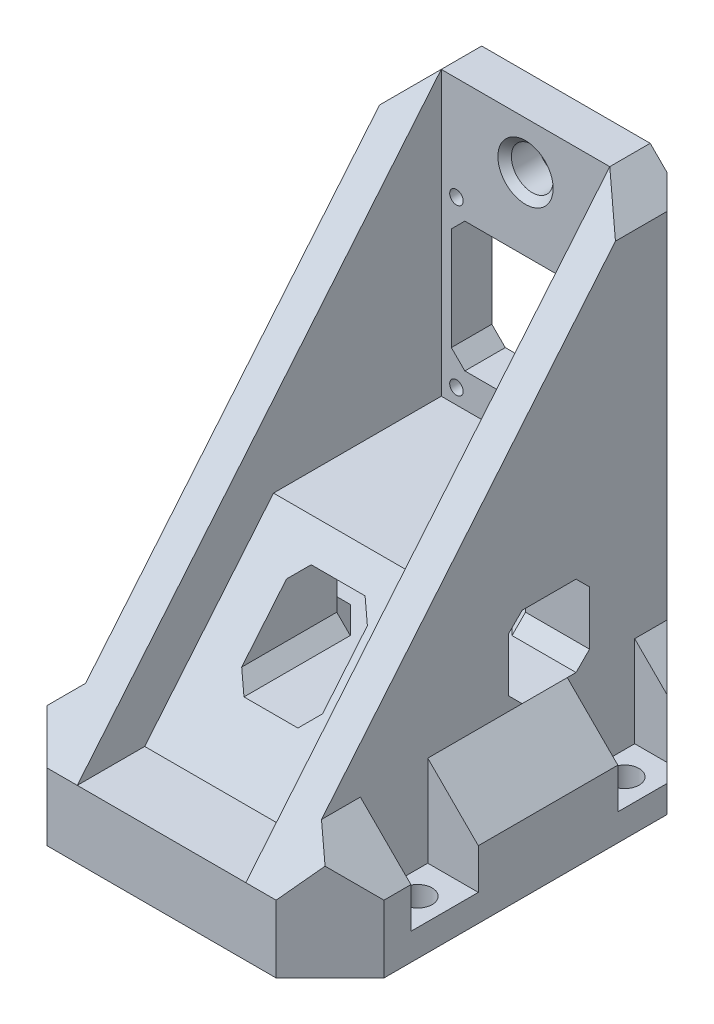
SolidWorks part; units mm, degrees
ref_plane "Front Plane" through (0, 0, 0) normal (0, 0, 1) x (1, 0, 0)
ref_plane "Top Plane" through (0, 0, 0) normal (0, 1, 0) x (1, 0, 0)
ref_plane "Right Plane" through (0, 0, 0) normal (1, 0, 0) x (0, 0, -1)
sketch "Sketch1" plane through (0, 0, 0) normal (0, 1, 0) x (1, 0, 0)
  line L1 (-25, 30) -> (25, 30)
  line L2 (-25, 30) -> (-25, -30)
  line L3 (-25, -30) -> (25, -30)
  line L4 (25, 30) -> (25, -30)
  line L5 (-25, 30) -> (25, -30) construction
  line L6 (-25, -30) -> (25, 30) construction
  point P0 (0, 0)
  dimension "D1" = 50
  dimension "D2" = 60
extrude "Boss-Extrude1" add sketch "Sketch1" along normal blind 10
sketch "Sketch2" plane through (0, 0, 0) normal (0, 1, 0) x (1, 0, 0)
  line L0 (-25, -30) -> (25, -30) construction
  line L1 (-21, -13) -> (21, -13) construction
  line L2 (-21, -13) -> (-21, 17.7) construction
  line L3 (-21, 17.7) -> (21, 17.7) construction
  line L4 (21, -13) -> (21, 17.7) construction
  line L5 (-21, -13) -> (21, 17.7) construction
  line L6 (-21, 17.7) -> (21, -13) construction
  circle A0 centre (-21, 17.7) radius 2.15
  circle A1 centre (-21, -13) radius 2.15
  circle A2 centre (21, 17.7) radius 2.15
  circle A3 centre (21, -13) radius 2.15
  point P0 (0, 2.35)
  dimension "D4" = 4.3
  dimension "D1" = 42
  dimension "D2" = 30.7
  dimension "D3" = 17
extrude "Cut-Extrude1" cut sketch "Sketch2" along normal blind 4
sketch "Sketch5" plane through (0, 10, 0) normal (0, 1, 0) x (1, 0, 0)
  line L0 (25, 30) -> (-25, 30) construction
  line L1 (-12.5, 24) -> (12.5, 24)
  line L2 (-12.5, 24) -> (-12.5, 30)
  line L3 (-12.5, 30) -> (12.5, 30)
  line L4 (12.5, 24) -> (12.5, 30)
  line L5 (-12.5, 24) -> (12.5, 30) construction
  line L6 (-12.5, 30) -> (12.5, 24) construction
  point P0 (0, 27)
  dimension "D1" = 6
  dimension "D2" = 25
extrude "Boss-Extrude3" add sketch "Sketch5" along normal blind 65
sketch "Sketch6" plane through (0, 0, -30) normal (0, 0, -1) x (-1, 0, 0)
  line L1 (-11, 38) -> (11, 38)
  line L2 (-11, 38) -> (-11, 57.25)
  line L3 (-11, 57.25) -> (11, 57.25)
  line L4 (11, 38) -> (11, 57.25)
  line L5 (-11, 38) -> (11, 57.25) construction
  line L6 (-11, 57.25) -> (11, 38) construction
  line L7 (-12.5, 75) -> (12.5, 75) construction
  point P0 (0, 47.625)
  dimension "D1" = 22
  dimension "D2" = 19.25
  dimension "D3" = 17.75
extrude "Cut-Extrude3" cut sketch "Sketch6" against normal up to next
sketch "Sketch7" plane through (0, 0, -24) normal (0, 0, 1) x (1, 0, 0)
  line L1 (-10.25, 35.25) -> (10.25, 35.25) construction
  line L2 (-10.25, 35.25) -> (-10.25, 59.7) construction
  line L3 (-10.25, 59.7) -> (10.25, 59.7) construction
  line L4 (10.25, 35.25) -> (10.25, 59.7) construction
  line L5 (-10.25, 35.25) -> (10.25, 59.7) construction
  line L6 (-10.25, 59.7) -> (10.25, 35.25) construction
  line L7 (-12.5, 75) -> (12.5, 75) construction
  circle A0 centre (10.25, 35.25) radius 1
  circle A1 centre (-10.25, 35.25) radius 1
  circle A2 centre (-10.25, 59.7) radius 1
  circle A3 centre (10.25, 59.7) radius 1
  point P0 (0, 47.475)
  dimension "D4" = 2
  dimension "D1" = 20.5
  dimension "D2" = 24.45
  dimension "D3" = 15.3
extrude "Cut-Extrude4" cut sketch "Sketch7" against normal blind 2.5
sketch "Sketch8" plane through (0, 0, -26.5) normal (0, 0, 1) x (1, 0, 0)
  circle A0 centre (-10.25, 59.7) radius 2
  circle A1 centre (10.25, 59.7) radius 2
  circle A2 centre (10.25, 35.25) radius 2
  circle A3 centre (-10.25, 35.25) radius 2
  dimension "D1" = 4
extrude "Cut-Extrude5" cut sketch "Sketch8" against normal up to next
sketch "Sketch9" plane through (12.5, 0, 0) normal (1, 0, 0) x (0, 0, -1)
  line L0 (30, 75) -> (24, 75)
  line L4 (-30, 10) -> (30, 10)
  line L5 (30, 10) -> (30, 75)
  line L6 (30, 75) -> (30, 10) construction
  line L8 (-30, 10) -> (24, 75)
extrude "Boss-Extrude4" add sketch "Sketch9" along normal blind 5
mirror "Mirror1" about plane through (0, 0, 0) normal (1, 0, 0) of "Boss-Extrude4"
chamfer "Chamfer1" distance 7.5 angle 45 2 edges at (17.5, 10, 0) (-17.5, 10, 0)
chamfer "Chamfer2" distance 10 angle 45 2 edges at (-25, 5, -30) (25, 5, -30)
chamfer "Chamfer4" distance 5.5 angle 45 1 edges at (0, 0, -30)
chamfer "Chamfer5" distance 5 angle 45 6 edges at (-15, 75, -24) (17.5, 75, -25.75) (-17.5, 75, -25.75) (16.25, 75, -28.75) (-16.25, 75, -28.75) (15, 75, -24)
chamfer "Chamfer7" distance 2 angle 45 4 edges at (-11, 57.25, -27) (-11, 38, -27) (11, 38, -27) (11, 57.25, -27)
sketch "Sketch10" plane through (0, 0, -30) normal (0, 0, -1) x (-1, 0, 0)
  circle A0 centre (0, 68) radius 3.1
  circle A1 centre (-10.25, 59.7) radius 2 construction
  dimension "D1" = 6.2
  dimension "D2" = 8.3
extrude "Cut-Extrude6" cut sketch "Sketch10" against normal up to next
chamfer "Chamfer8" distance 1 angle 45 2 edges at (-3.1, 68, -24) (-3.1, 68, -30)
sketch "Sketch11" plane through (-12.5, 0, 0) normal (1, 0, 0) x (0, 0, -1)
  line L0 (-20, 10) -> (24, 10)
  line L1 (24, 10) -> (24, 33)
  line L2 (24, 75) -> (24, 10) construction
  line L3 (24, 33) -> (-0.8923, 33)
  line L4 (30, 38) -> (24, 38) construction
  line L5 (-0.8923, 33) -> (-20, 10)
  line L7 (19.8462, 70) -> (-23.7692, 17.5) construction
  line L9 (-30, 10) -> (20, 10) construction
  dimension "D1" = 5
  dimension "D2" = 10
extrude "Boss-Extrude5" add sketch "Sketch11" along normal up to next
chamfer "Chamfer9" distance 8 angle 45 2 edges at (-25, 5, 30) (25, 5, 30)
sketch "Sketch12" plane through (0, 0, -30) normal (0, 0, -1) x (-1, 0, 0)
  line L1 (-6, 17.5) -> (6, 17.5)
  line L2 (-6, 17.5) -> (-6, 29.5)
  line L3 (-6, 29.5) -> (6, 29.5)
  line L4 (6, 17.5) -> (6, 29.5)
  line L5 (-6, 17.5) -> (6, 29.5) construction
  line L6 (-6, 29.5) -> (6, 17.5) construction
  point P0 (0, 23.5)
  dimension "D1" = 12
extrude "Cut-Extrude7" cut sketch "Sketch12" against normal up to next contours L2 L3 L4 L1
sketch "Sketch14" plane through (-6, 0, 0) normal (1, 0, 0) x (0, 0, -1)
  line L0 (-13.7692, 17.5) -> (30, 17.5) construction
  line L5 (30, 17.5) -> (30, 29.5) construction
  line L6 (-3.8, 29.5) -> (30, 29.5) construction
  line L7 (4, 17.5) -> (16, 17.5)
  line L8 (4, 17.5) -> (4, 29.5)
  line L9 (4, 29.5) -> (16, 29.5)
  line L10 (16, 17.5) -> (16, 29.5)
  line L11 (4, 17.5) -> (16, 29.5) construction
  line L12 (4, 29.5) -> (16, 17.5) construction
  point P0 (10, 23.5)
  dimension "D1" = 20
extrude "Cut-Extrude9" cut sketch "Sketch14" against normal up to next
mirror "Mirror2" about plane through (0, 0, 0) normal (1, 0, 0) of "Cut-Extrude9"
chamfer "Chamfer11" distance 2 angle 45 20 edges at (11.75, 29.5, -16) (6, 29.5, -23) (6, 23.5, -16) (11.75, 17.5, -16) (6, 17.5, -23) (-11.75, 17.5, -16) (-6, 17.5, -23) (-6, 23.5, -16) (-11.75, 29.5, -16) (-6, 29.5, -23) (11.75, 17.5, -4) (6, 17.5, 4.8846) (6, 23.5, -4) (11.75, 29.5, -4) (6, 29.5, -0.1) (-11.75, 17.5, -4) (-6, 17.5, 4.8846) (-6, 23.5, -4) (-11.75, 29.5, -4) (-6, 29.5, -0.1)
sketch "Sketch16" plane through (17.5, 0, 0) normal (1, 0, 0) x (0, 0, -1)
  line L0 (-23.7692, 17.5) -> (6, 17.5) construction
  line L1 (-18, 17.5) -> (-8, 17.5)
  line L2 (-18, 17.5) -> (-18, 4)
  line L3 (-18, 4) -> (-8, 4)
  line L4 (-8, 17.5) -> (-8, 4)
  line L5 (-15.15, 4) -> (-10.85, 4) construction
  line L6 (-8, 4) -> (-18, 17.5) construction
  line L7 (-30, 0) -> (-30, 10) construction
  point P8 (-13, 10.75)
  dimension "D1" = 10
  dimension "D2" = 17
extrude "Cut-Extrude11" cut sketch "Sketch16" along normal up to next
sketch "Sketch17" plane through (17.5, 0, 0) normal (1, 0, 0) x (0, 0, -1)
  line L0 (14, 17.5) -> (27.5, 17.5) construction
  line L1 (12.7, 4) -> (22.7, 4)
  line L2 (12.7, 4) -> (12.7, 17.5)
  line L3 (12.7, 17.5) -> (22.7, 17.5)
  line L4 (22.7, 4) -> (22.7, 17.5)
  line L5 (15.55, 4) -> (19.85, 4) construction
  line L6 (12.7, 17.5) -> (22.7, 4) construction
  line L7 (30, 72.5) -> (30, 5.5) construction
  point P8 (17.7, 10.75)
  dimension "D1" = 10
  dimension "D2" = 12.3
extrude "Cut-Extrude12" cut sketch "Sketch17" along normal up to next
mirror "Mirror4" about plane through (0, 0, 0) normal (1, 0, 0) of "Cut-Extrude12", "Cut-Extrude11"
